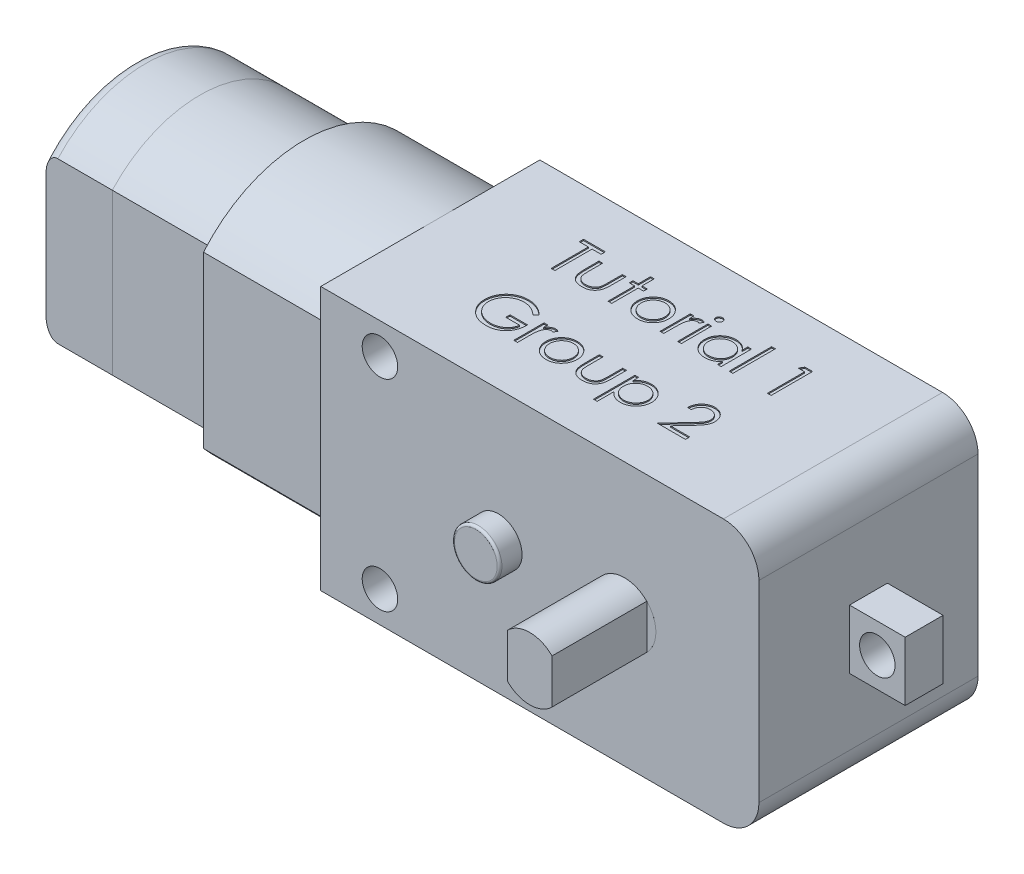
SolidWorks part; units mm, degrees
other "Markup1"
sketch "Sketch1" plane through (23.2, -11.125, 17.75) normal (0.3723, -0.0119, 0.928) x (0.9281, 0.003, -0.3723)
sketch "Sketch20" plane through (23.2, -11.125, 17.25) normal (0.3723, -0.0119, 0.928) x (0.9281, 0.003, -0.3723)
ref_plane "Front Plane" through (0, 0, 0) normal (0, 0, 1) x (1, 0, 0)
ref_plane "Top Plane" through (0, 0, 0) normal (0, 1, 0) x (1, 0, 0)
ref_plane "Right Plane" through (0, 0, 0) normal (1, 0, 0) x (0, 0, -1)
sketch "Sketch 1" plane through (0, 0, 0) normal (0, 0, 1) x (1, 0, 0)
  line L1 (-18.5, -11.125) -> (15.5, -11.125)
  line L2 (-18.5, -11.125) -> (-18.5, 11.125)
  line L3 (-18.5, 11.125) -> (15.5, 11.125)
  line L4 (18.5, -8.125) -> (18.5, 8.125)
  line L5 (-18.5, -11.125) -> (18.5, 11.125) construction
  line L6 (-18.5, 11.125) -> (18.5, -11.125) construction
  arc A0 (15.5, -11.125) -> (18.5, -8.125) centre (15.5, -8.125) ccw
  arc A1 (15.5, 11.125) -> (18.5, 8.125) centre (15.5, 8.125) cw
  point P0 (0, 0)
  dimension "D3" = 3
  dimension "D1" = 22.25
  dimension "D2" = 37
extrude "Boss-Extrude1" add sketch "Sketch 1" along normal blind 9.25 and the other way blind 9.25
sketch "Sketch2" plane through (-18.5, 0, 0) normal (-1, 0, 0) x (0, 0, 1)
  line L0 (-0.75, -11.125) -> (-0.75, 11.125) construction
  line L1 (7.75, -7.1774) -> (7.75, 7.1774)
  line L2 (-9.25, -7.1774) -> (-9.25, 7.1774)
  line L3 (9.25, 11.125) -> (9.25, -11.125) construction
  line L5 (7.75, -12.1318) -> (7.75, 11.125) construction
  line L6 (-9.25, -12.1318) -> (-9.25, 11.125) construction
  line L7 (-0.75, -12.1318) -> (-0.75, 11.125) construction
  arc A0 (7.75, 7.1774) -> (-9.25, 7.1774) centre (-0.75, 0) ccw
  arc A1 (-9.25, -7.1774) -> (7.75, -7.1774) centre (-0.75, 0) ccw
  point P8 (-0.75, 0)
  dimension "D1" = 22.25
  dimension "D2" = 8.5
  dimension "D3" = 8.5
  dimension "D4" = 1.5
extrude "Boss-Extrude2" add sketch "Sketch2" along normal blind 11.4
sketch "Sketch3" plane through (18.5, 0, 0) normal (1, 0, 0) x (0, 0, -1)
  line L1 (1.6, -2.5) -> (-1.6, -2.5)
  line L2 (1.6, -2.5) -> (1.6, 2.5)
  line L3 (1.6, 2.5) -> (-1.6, 2.5)
  line L4 (-1.6, -2.5) -> (-1.6, 2.5)
  line L5 (1.6, -2.5) -> (-1.6, 2.5) construction
  line L6 (1.6, 2.5) -> (-1.6, -2.5) construction
  point P0 (0, 0)
  dimension "D1" = 5
  dimension "D2" = 3.2
extrude "Boss-Extrude3" add sketch "Sketch3" along normal blind 4.7
sketch "Sketch4" plane through (0, 0, 0) normal (0, 0, 1) x (1, 0, 0)
  line L0 (0, 0) -> (-18.2045, 0) construction
  line L3 (-18.5, 11.125) -> (-18.5, -11.125) construction
  circle A0 centre (-13.5, 8.5) radius 1.5
  circle A1 centre (-13.5, -8.5) radius 1.5
  dimension "D1" = 3
  dimension "D2" = 17
  dimension "D5" = 5
extrude "Cut-Extrude1" cut sketch "Sketch4" against normal blind 17.7 and the other way blind 28
sketch "Sketch5" plane through (0, 0, 9.25) normal (0, 0, 1) x (1, 0, 0)
  line L0 (18.5, -8.125) -> (18.5, 8.125) construction
  circle A0 centre (-3.5, 0) radius 2
  point P6 (18.5, 0)
  dimension "D1" = 4
  dimension "D2" = 22
extrude "Boss-Extrude4" add sketch "Sketch5" along normal blind 1.9
fillet "Fillet1" radius 0.2 1 edges at (-1.5, 0, 11.15)
sketch "Sketch6" plane through (0, 0, 9.25) normal (0, 0, 1) x (1, 0, 0)
  line L0 (18.5, -8.125) -> (18.5, 8.125) construction
  circle A0 centre (7.15, 0) radius 2.65
  dimension "D1" = 5.3
  dimension "D2" = 11.35
extrude "Cut-Extrude2" cut sketch "Sketch6" against normal blind 23.9
sketch "Sketch9" plane through (-29.9, 0, 0) normal (-1, 0, 0) x (0, 0, 1)
  line L2 (6.65, -7.1774) -> (6.65, 7.1774)
  line L3 (6.65, -6.7632) -> (6.65, 6.7632)
  line L5 (-8.15, 7.1774) -> (-8.15, -7.1774)
  line L6 (-8.15, 6.7632) -> (-8.15, -6.7632)
  arc A2 (6.9096, 6.4678) -> (-8.4096, 6.4678) centre (-0.75, 0) ccw
  arc A3 (6.65, 6.7632) -> (-8.15, 6.7632) centre (-0.75, 0) ccw
  arc A5 (-8.4096, -6.4678) -> (6.9096, -6.4678) centre (-0.75, 0) ccw
  arc A6 (-8.15, -6.7632) -> (6.65, -6.7632) centre (-0.75, 0) ccw
  dimension "D1" = 1.1
  dimension "D2" = 1.1
  dimension "D3" = 1.1
  dimension "D4" = 1.1
extrude "Boss-Extrude5" add sketch "Sketch9" along normal blind 8.8 separate body
sketch "Sketch10" plane through (-38.7, 0, 0) normal (-1, 0, 0) x (0, 0, 1)
  line L0 (-8.15, 6.7632) -> (-8.15, -6.7632)
  line L1 (6.65, 6.7632) -> (6.65, -6.7632)
  line L2 (6.65, -6.7632) -> (6.65, 6.7632) construction
  arc A0 (6.65, 6.7632) -> (-8.15, 6.7632) centre (-0.75, 0) ccw
  arc A1 (6.65, 6.7632) -> (-8.15, 6.7632) centre (-0.75, 0) ccw construction
  arc A2 (-8.15, -6.7632) -> (6.65, -6.7632) centre (-0.75, 0) ccw
extrude "Boss-Extrude6" add sketch "Sketch10" along normal blind 5.6 separate body
fillet "Fillet2" radius 1 2 edges at (-44.3, 10.025, -0.75) (-44.3, -10.025, -0.75)
sketch "Sketch11" plane through (-44.3, 0, 0) normal (-1, 0, 0) x (0, 0, 1)
  line L0 (6.65, 5.1663) -> (6.65, -7.0924) construction
  line L1 (6.65, -6.7632) -> (6.65, -5.1663) construction
  line L2 (2.65, 3.6661) -> (2.65, -3.6661)
  line L3 (2.65, 5.1663) -> (2.65, -7.0924) construction
  arc A0 (2.65, 3.6661) -> (2.65, -3.6661) centre (-0.75, 0) ccw
  arc A2 (6.65, 6.7632) -> (-8.15, 6.7632) centre (-0.75, 0) ccw construction
  dimension "D1" = 10
  dimension "D2" = 4
extrude "Boss-Extrude7" add sketch "Sketch11" along normal blind 1 separate body
sketch "Sketch12" plane through (-45.3, 0, 0) normal (-1, 0, 0) x (0, 0, 1)
  circle A0 centre (-0.75, 0) radius 1
  arc A1 (2.65, 3.6661) -> (2.65, -3.6661) centre (-0.75, 0) ccw construction
  dimension "D1" = 2
extrude "Boss-Extrude8" add sketch "Sketch12" along normal blind 0.5 separate body
sketch "Sketch14" plane through (0, 0, 1.6) normal (0, 0, 1) x (1, 0, 0)
  line L0 (18.5, 2.5) -> (23.2, -2.5) construction
  line L1 (23.2, 2.5) -> (18.5, -2.5) construction
  circle A0 centre (20.85, 0) radius 1.5
  dimension "D1" = 3
extrude "Cut-Extrude3" cut sketch "Sketch14" against normal blind 4.2
sketch "Sketch15" plane through (0, 0, 0) normal (0, 0, 1) x (1, 0, 0)
  line L0 (7.15, -5.2054) -> (7.15, 5.2054) construction
  line L1 (9.03, -1.8676) -> (9.03, 1.8676)
  line L2 (5.27, -1.8676) -> (5.27, 1.8676)
  line L3 (9.03, -5.2054) -> (9.03, 5.2054) construction
  line L4 (5.27, -5.2054) -> (5.27, 5.2054) construction
  arc A0 (5.27, -1.8676) -> (9.03, -1.8676) centre (7.15, 0) ccw
  circle A1 centre (7.15, 0) radius 2.65 construction
  arc A2 (9.03, 1.8676) -> (5.27, 1.8676) centre (7.15, 0) ccw
  point P7 (7.15, 0)
  dimension "D1" = 3.76
extrude "Boss-Extrude10" add sketch "Sketch15" along normal blind 17.25 and the other way blind 17.25 separate body
sketch "Sketch16" plane through (0, 0, 0) normal (0, 0, 1) x (1, 0, 0)
  circle A0 centre (7.15, 0) radius 2.65
  circle A1 centre (7.15, 0) radius 2.65 construction
extrude "Boss-Extrude11" add sketch "Sketch16" along normal up to surface and the other way up to surface separate body up to face at (9.8, 0, 9.25) other way up to face at (4.5, 0, -9.25)
sketch "Sketch19" plane through (0, 11.125, 0) normal (0, 1, 0) x (1, 0, 0)
  text T0 "Tutorial 1\r\nGroup 2"
extrude "Cut-Extrude4" cut sketch "Sketch19" against normal blind 0.1
